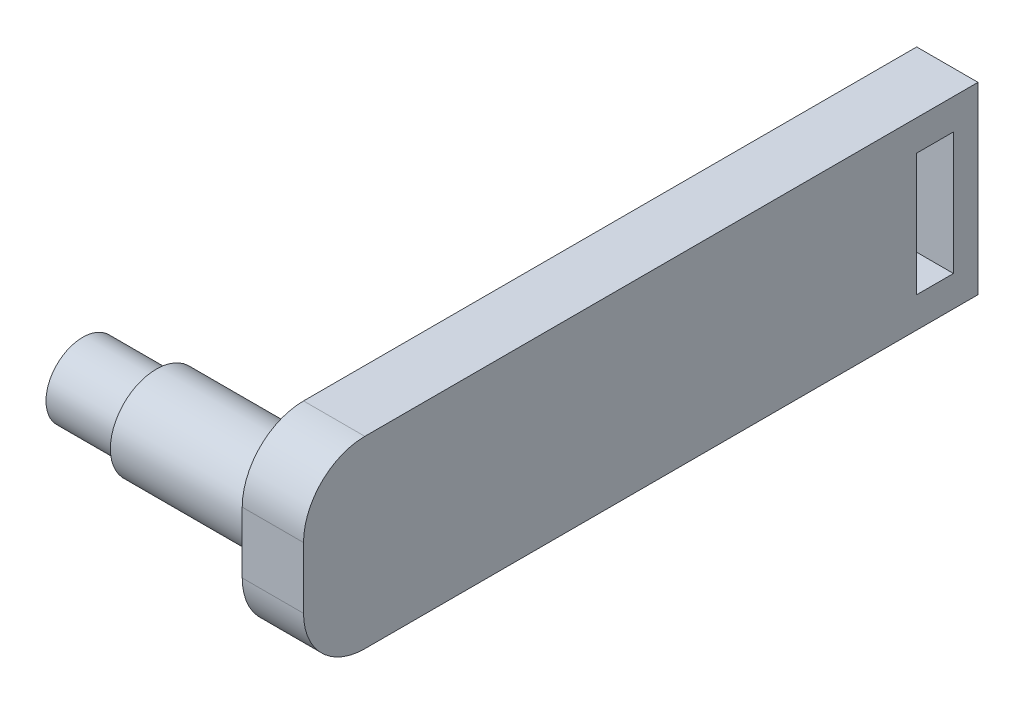
SolidWorks part; units mm, degrees
ref_plane "Front Plane" through (0, 0, 0) normal (0, 0, 1) x (1, 0, 0)
ref_plane "Top Plane" through (0, 0, 0) normal (0, 1, 0) x (1, 0, 0)
ref_plane "Right Plane" through (0, 0, 0) normal (1, 0, 0) x (0, 0, -1)
sketch "Sketch1" plane through (0, 0, 0) normal (0, 1, 0) x (1, 0, 0)
  line L1 (-61.8805, -26.2097) -> (-56.8805, -26.2097)
  line L2 (-61.8805, -26.2097) -> (-61.8805, 28.7903)
  line L3 (-61.8805, 28.7903) -> (-56.8805, 28.7903)
  line L4 (-56.8805, -26.2097) -> (-56.8805, 28.7903)
  line L6 (-56.8805, 28.7903) -> (-56.8805, 23.7903)
  dimension "D5" = 5
extrude "Boss-Extrude1" add sketch "Sketch1" along normal blind 15 contours L1 L4 L3 L2 region at (-59.3805, 0, -1.2903)
sketch "Sketch2" plane through (-61.8805, 0, 0) normal (-1, 0, 0) x (0, 0, 1)
  line L2 (26.2097, 0) -> (-28.7903, 0) construction
  line L3 (-28.7903, 15) -> (-28.7903, 0) construction
  line L5 (-26.7903, 2.5) -> (-23.7903, 2.5)
  line L6 (-26.7903, 2.5) -> (-26.7903, 12.5)
  line L7 (-26.7903, 12.5) -> (-23.7903, 12.5)
  line L8 (-23.7903, 2.5) -> (-23.7903, 12.5)
  dimension "D4" = 2.5
  dimension "D5" = 10
  dimension "D6" = 2
  dimension "D7" = 3
fillet "Fillet1" radius 5 2 edges at (-59.3805, 15, 26.2097) (-59.3805, 0, 26.2097)
sketch "Sketch3" plane through (-61.8805, 0, 0) normal (-1, 0, 0) x (0, 0, 1)
  line L3 (21.2097, 15) -> (-28.7903, 15) construction
  line L4 (26.2097, 10) -> (26.2097, 5) construction
  circle A1 centre (21.2097, 7.5) radius 3.75
  dimension "D1" = 7.5
  dimension "D2" = 5
  dimension "D3" = 7.5
extrude "Cut-Extrude1" cut sketch "Sketch2" against normal up to surface (5 mm away) up to face at (-56.8805, 7.5, 6.5549)
extrude "Boss-Extrude2" add sketch "Sketch3" along normal blind 12
sketch "Sketch4" plane through (-73.8805, 0, 0) normal (-1, 0, 0) x (0, 0, 1)
  circle A0 centre (21.2097, 7.5) radius 3
  circle A1 centre (21.2097, 7.5) radius 1.75
extrude "Boss-Extrude3" add sketch "Sketch4" along normal blind 6
